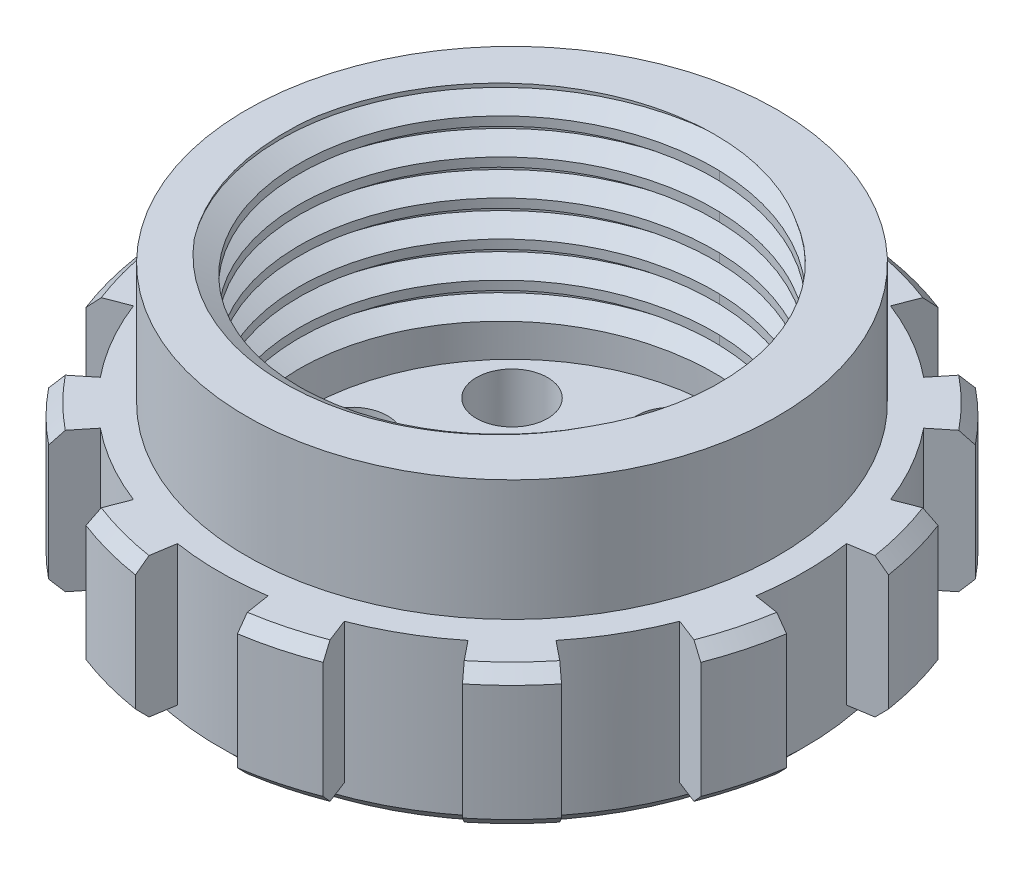
SolidWorks part; units mm, degrees
ref_plane "Front" through (0, 0, 0) normal (0, 0, 1) x (1, 0, 0)
ref_plane "Top" through (0, 0, 0) normal (0, 1, 0) x (1, 0, 0)
ref_plane "Right" through (0, 0, 0) normal (1, 0, 0) x (0, 0, -1)
sketch "Sketch1" plane through (0, 0, 0) normal (0, 0, 1) x (1, 0, 0)
  line L0 (0, 0) -> (0, 50.9403) construction
  line L1 (0, 0) -> (13.9, 0)
  line L2 (13.9, 0) -> (13.9, 6.9)
  line L3 (13.9, 6.9) -> (11.2, 6.9)
  line L4 (11.2, 6.9) -> (11.2, 12)
  line L5 (11.2, 12) -> (8.75, 12)
  line L6 (8.75, 12) -> (8.75, 2.3)
  line L7 (8.75, 2.3) -> (0, 2.3)
  line L8 (0, 2.3) -> (0, 0)
  dimension "D1" = 27.8
  dimension "D2" = 6.9
  dimension "D3" = 22.4
  dimension "D4" = 12
  dimension "D5" = 17.5
  dimension "D6" = 9.7
revolve "Revolve1" add sketch "Sketch1" angle 360 about L0
sketch "Sketch2" plane through (0, 2.3, 0) normal (0, 1, 0) x (1, 0, 0)
  circle A0 centre (0, 0) radius 3.5
  circle A1 centre (6.75, 0) radius 1.5
  dimension "D1" = 7
  dimension "D2" = 3
  dimension "D3" = 6.75
extrude "Cut-Extrude1" cut sketch "Sketch2" against normal blind 10
pattern_circular "CirPattern1" count 8 over 360 about axis through (0, 12, 0) along (0, -1, 0) of "Cut-Extrude1"
chamfer "Chamfer1" distance 0.5 angle 45 1 edges at (0, 6.9, -13.9)
sketch "Sketch3" plane through (0, 0, 0) normal (0, -1, 0) x (1, 0, 0)
  line L0 (12.35, 0) -> (15.2865, 0) construction
  line L6 (13.7327, 2.15) -> (12.2014, 1.9103)
  line L7 (12.2014, -1.9103) -> (13.7327, -2.15)
  arc A0 (13.7327, -2.15) -> (13.7327, 2.15) centre (0, 0) ccw
  arc A1 (12.2014, -1.9103) -> (12.2014, 1.9103) centre (0, 0) ccw
  dimension "D3" = 24.7
extrude "Cut-Extrude2" cut sketch "Sketch3" against normal blind 10
pattern_circular "CirPattern2" count 12 over 360 about axis through (0, 0, 0) along (0, -1, 0) of "Cut-Extrude2"
sketch "Sketch4" plane through (0, 0, 0) normal (0, -1, 0) x (1, 0, 0)
  circle A0 centre (0, 0) radius 13.9
  circle A1 centre (0, 0) radius 12.35
extrude "Cut-Extrude3" cut sketch "Sketch4" against normal blind 1
chamfer "Chamfer2" distance 0.5 angle 45 13 edges at (0, 0, -12.35) (-13.4264, 1, -3.5976) (-9.8288, 1, -9.8288) (-3.5976, 1, -13.4264) (3.5976, 1, -13.4264) (9.8288, 1, -9.8288) (13.4264, 1, -3.5976) (13.4264, 1, 3.5976) (9.8288, 1, 9.8288) (-13.4264, 1, 3.5976) (-9.8288, 1, 9.8288) (-3.5976, 1, 13.4264) (3.5976, 1, 13.4264)
thread "Thread1" pitch 1.5 method cut profile "Thread Profile1" start angle 0, offset 2, length 10, pitch 1.5, diameter 17.5
ref_plane "Plane1" through (-8.75, 14, 0) normal (0, 0, 1) x (-1, 0, 0)
sketch "Thread Profile1" plane through (-8.75, 14, 0) normal (0, 0, 1) x (-1, 0, 0)
  line L0 (0, 0) -> (0, 1.5) construction
  line L1 (0, 0) -> (0.8119, 0.4687)
  line L2 (0.8119, 0.4687) -> (0.8119, 0.6562)
  line L3 (0.8119, 0.6562) -> (0, 1.125)
  line L4 (0.8119, 0.5625) -> (0, 0.5625) construction
  line L11 (0, 0) -> (0, 1.125)
  point P2 (0, 0)
  dimension "Pitch" = 1.5
  dimension "Profile_Angle" = 60
  dimension "Profile_Land" = 0.1875
  dimension "Profile_Height" = 0.8119
